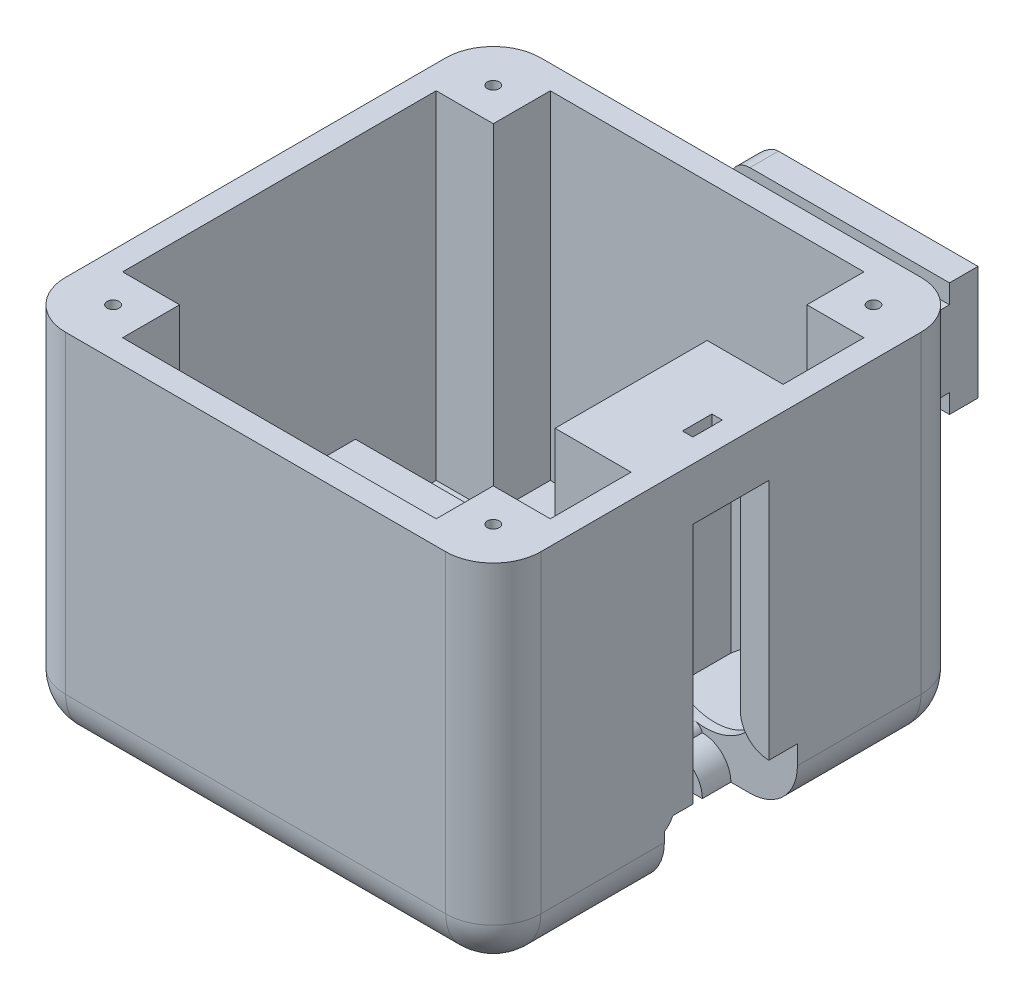
SolidWorks part; units mm, degrees
ref_plane "Front Plane" through (0, 0, 0) normal (0, 0, 1) x (1, 0, 0)
ref_plane "Top Plane" through (0, 0, 0) normal (0, 1, 0) x (1, 0, 0)
ref_plane "Right Plane" through (0, 0, 0) normal (1, 0, 0) x (0, 0, -1)
sketch "Sketch1" plane through (0, 0, 0) normal (0, 1, 0) x (1, 0, 0)
  line L1 (25, 25) -> (-25, 25)
  line L2 (25, 25) -> (25, -25)
  line L3 (25, -25) -> (-25, -25)
  line L4 (-25, 25) -> (-25, -25)
  line L5 (25, 25) -> (-25, -25) construction
  line L6 (25, -25) -> (-25, 25) construction
  point P0 (0, 0)
  dimension "D1" = 50
  dimension "D2" = 50
extrude "Boss-Extrude1" add sketch "Sketch1" along normal blind 38
shell "Shell1" thickness 2.5 removed face at (0, 38, 0)
sketch "Sketch2" plane through (0, 2.5, 0) normal (0, 1, 0) x (1, 0, 0)
  line L1 (9.676, 17.0496) -> (-10.324, 17.0496) construction
  line L2 (9.676, 17.0496) -> (9.676, -16.9504) construction
  line L3 (-10.3, -16.9504) -> (-10.324, -16.9504) construction
  line L4 (-10.324, 17.0496) -> (-10.324, -16.9504) construction
  line L5 (-10.3, 6.5) -> (-22.5, 6.5)
  line L6 (-22.5, 22.5) -> (-22.5, -22.5) construction
  line L7 (-22.5, 6.5) -> (-22.5, 22.5)
  line L8 (-22.5, 22.5) -> (0, 22.5)
  line L9 (22.5, 22.5) -> (-22.5, 22.5) construction
  line L11 (-10.3, 6.5) -> (-10.3, 13.5)
  line L12 (-10.3, 13.5) -> (0, 13.5)
  line L14 (22.5, 7.28) -> (22.5, 22.5)
  line L15 (10.3, 7.28) -> (22.5, 7.28)
  line L16 (10.3, 7.28) -> (10.3, 13.5)
  line L17 (10.3, 13.5) -> (0, 13.5)
  line L19 (22.5, 22.5) -> (0, 22.5)
  line L20 (10.3, -13.3556) -> (22.5, -13.3556)
  line L22 (10.0266, -9.8035) -> (10.0241, -17.0234) construction
  line L27 (-22.5, -13.6) -> (-22.5, -22.5)
  line L28 (-10.3, -13.6) -> (-22.5, -13.6)
  line L29 (-10.3, -13.6) -> (-10.3, -20.79)
  line L30 (-10.3, -20.79) -> (0.1901, -20.79)
  line L32 (-22.5, -22.5) -> (0.1901, -22.5)
  line L33 (-10.324, 17.0496) -> (-10.324, 9.8396) construction
  line L34 (10.3, -13.3556) -> (10.3, -20.79)
  line L35 (9.676, -16.9504) -> (-10.3, -16.9504) construction
  line L36 (10.3, -20.79) -> (0.1901, -20.79)
  line L38 (22.5, -22.5) -> (0.1901, -22.5)
  line L39 (22.5, -13.3556) -> (22.5, -22.5)
  line L40 (22.5, -22.5) -> (22.5, 22.5) construction
  point P0 (0, 0)
  dimension "D1" = 34
  dimension "D3" = 12.2
  dimension "D4" = 12.2
  dimension "D5" = 16
  dimension "D6" = 8.9
  dimension "D7" = 9
  dimension "D9" = 1.71
sketch "Sketch3" plane through (0, 2.5, 0) normal (0, 1, 0) x (1, 0, 0)
  line L0 (22.5, -8) -> (22.5, 8)
  line L1 (22.5, -22.5) -> (22.5, 22.5) construction
  line L2 (22.5, 8) -> (22.5, -8)
  line L3 (22.5, 8) -> (-22.5, 8)
  line L4 (22.5, -8) -> (-22.5, -8)
  line L5 (-22.5, 8) -> (-22.5, -8)
  line L6 (-22.5, 22.5) -> (-22.5, -22.5) construction
  point P4 (22.5, 0)
  point P6 (22.5, 0)
  line M6 (-22.5, 22.5) -> (-22.5, -22.5)
  line M8 (22.5, -22.5) -> (22.5, 22.5)
  dimension "D1" = 16
extrude "Boss-Extrude3" add sketch "Sketch3" along normal blind 8 contours L4 L3 M8 M6 region at (0, 2.5, 0)
sketch "Sketch4" plane through (0, 0, 0) normal (0, -1, 0) x (1, 0, 0)
  line L4 (25, -4) -> (-7.5, -4)
  line L5 (22.5, -8) -> (25, -8) construction
  line L6 (22.5, 8) -> (25, 8) construction
  line L7 (22.5, 0) -> (25, 0)
  line L8 (25, 25) -> (25, -25) construction
  line L9 (-7.5, -4) -> (-7.5, 4)
  line L10 (-7.5, 4) -> (25, 4)
  line L11 (25, 4) -> (25, -4)
  point P10 (25, 0)
  line M10 (25, -25) -> (25, 25)
  dimension "D1" = 8
  dimension "D2" = 32.5
extrude "Cut-Extrude1" cut sketch "Sketch4" against normal blind 3 contours L10 L9 L4 M10 region at (8.75, 0, 0)
ref_plane "Plane1" through (0, 3, 0) normal (0, -1, 0) x (-1, 0, 0)
sketch "Sketch7" plane through (0, 3, 0) normal (0, -1, 0) x (-1, 0, 0)
  line L5 (-25, 4) -> (-25, -4) construction
  line L6 (-25, -6) -> (-25, 6)
  line L7 (-25, -6) -> (7.5, -6)
  line L8 (-25, 6) -> (7.5, 6)
  line L9 (7.5, -6) -> (7.5, 6)
  line L10 (-25, -25) -> (-25, -4) construction
  line L11 (-25, 4) -> (-25, 25) construction
  point P4 (-25, 0)
  point P11 (-25, 0)
  dimension "D1" = 12
  dimension "D2" = 32.5
extrude "Cut-Extrude2" cut sketch "Sketch7" against normal blind 3
sketch "Sketch8" plane through (22.5, 0, 0) normal (-1, 0, 0) x (0, 0, 1)
  line L0 (-8, 10.5) -> (-8, 38)
  line L1 (22.5, 38) -> (-22.5, 38) construction
  line L2 (8, 10.5) -> (8, 38)
  line L3 (8, 38) -> (-8, 38)
  line L4 (-8, 10.5) -> (8, 10.5)
extrude "Boss-Extrude4" add sketch "Sketch8" along normal blind 8
sketch "Sketch9" plane through (25, 0, 0) normal (1, 0, 0) x (0, 0, -1)
  line L0 (-4, 0) -> (-4, 32.5)
  line L2 (4, 0) -> (4, 32.5)
  line L3 (4, 32.5) -> (-4, 32.5)
  line L4 (-4, 0) -> (4, 0)
  dimension "D1" = 32.5
extrude "Cut-Extrude3" cut sketch "Sketch9" against normal blind 3 contours L4 L2 L3 L0
ref_plane "Plane2" through (22, 0, 0) normal (1, 0, 0) x (0, 0, -1)
sketch "Sketch10" plane through (22, 0, 0) normal (1, 0, 0) x (0, 0, -1)
  line L0 (-6, 0) -> (-6, 32.5)
  line L1 (-25, 0) -> (-4, 0) construction
  line L3 (6, 3) -> (6, 0)
  line L4 (4, 0) -> (25, 0) construction
  line L5 (6, 0) -> (6, 32.5)
  line L7 (6, 32.5) -> (-6, 32.5)
  line L8 (-6, 0) -> (6, 0)
  dimension "D1" = 32.5
extrude "Cut-Extrude5" cut sketch "Sketch10" against normal blind 3 contours L0 L8 L3 L5 L7 region at (22, 16.25, 0)
ref_plane "Plane3" through (0, 0, 4) normal (0, 0, -1) x (-1, 0, 0)
sketch "Sketch13" plane through (0, 0, 4) normal (0, 0, -1) x (-1, 0, 0)
  line L0 (-25, 0) -> (-22, 0)
  line L1 (-25, 0) -> (-25, 3.0115)
  line L2 (-22, 0) -> (-22, 3.0115)
  line L3 (-25, 3.0115) -> (-22, 3.0115)
extrude "Cut-Extrude7" cut sketch "Sketch13" against normal blind 2 and the other way blind 10
ref_plane "Plane4" through (0, 0, 6) normal (0, 0, -1) x (-1, 0, 0)
fillet "Fillet1" radius 5 9 edges at (-25, 19, 25) (25, 19, 25) (25, 19, -25) (-25, 19, -25) (-25, 0, 0) (0, 0, 25) (25, 0, 15.5) (0, 0, -25) (25, 0, -15.5)
ref_plane "Plane6" through (0, 0, 1.5) normal (0, 0, -1) x (-1, 0, 0)
sketch "Sketch16" plane through (0, 0, 1.5) normal (0, 0, -1) x (-1, 0, 0)
  line L0 (-25, 9.7) -> (-25, 0) construction
  line L1 (-17.6, 9.7) -> (-15.3, 9.7) construction
  line L2 (-25, 0) -> (-15.3, 0) construction
  line L3 (-15.3, 9.7) -> (-15.3, 7.4) construction
  line L5 (-15.3, 7.4) -> (-15.3, 0) construction
  line L6 (-25, 9.7) -> (-17.6, 9.7) construction
  circle A0 centre (-15.3, 9.7) radius 2.3
  dimension "D3" = 4.6
  dimension "D1" = 9.7
  dimension "D2" = 9.7
extrude "Cut-Extrude8" cut sketch "Sketch16" along normal through all
sketch "Sketch17" plane through (0, 0, -25) normal (0, 0, -1) x (-1, 0, 0)
  line L0 (-20, 36) -> (3, 36)
  line L1 (-20, 38) -> (-20, 5) construction
  line L2 (3, 36) -> (3, 24)
  line L3 (3, 24) -> (-20, 24)
  line L4 (-20, 24) -> (-20, 36)
  line L5 (-20, 38) -> (20, 38) construction
  dimension "D1" = 12
  dimension "D2" = 23
  dimension "D3" = 2
extrude "Boss-Extrude5" add sketch "Sketch17" along normal blind 6
sketch "Sketch18" plane through (-3, 0, 0) normal (-1, 0, 0) x (0, 0, 1)
  line L0 (-31, 30) -> (-25, 30) construction
  line L1 (-31, 24) -> (-31, 36) construction
  line L2 (-25, 24) -> (-25, 36) construction
  line L3 (-28, 24) -> (-25, 24)
  line L4 (-28, 24) -> (-28, 26)
  line L5 (-25, 24) -> (-25, 26)
  line L6 (-28, 26) -> (-25, 26)
  line L7 (-31, 24) -> (-25, 24) construction
  line L8 (-25, 36) -> (-25, 34)
  line L9 (-28, 34) -> (-25, 34)
  line L10 (-28, 36) -> (-28, 34)
  line L11 (-28, 36) -> (-25, 36)
  dimension "D1" = 4
extrude "Cut-Extrude9" cut sketch "Sketch18" against normal through all
ref_plane "Plane5" through (0, 0, -25) normal (0, 0, -1) x (-1, 0, 0)
sketch "Sketch20" plane through (0, 0, 4) normal (0, 0, -1) x (-1, 0, 0)
  line L0 (-22, 6) -> (-22, 32.5) construction
  line L2 (-22, 10) -> (-22, 7)
  line L7 (-22, 6) -> (-25, 6) construction
  line L8 (-24, 6) -> (-22, 6)
  line L9 (-22, 6) -> (-22, 7)
  line L10 (-24, 6) -> (-25, 6)
  line L11 (-25, 6) -> (-25, 7)
  line L12 (-25, 6) -> (-25, 32.5) construction
  arc A0 (-25, 7) -> (-22, 10) centre (-25, 10) ccw
  dimension "D1" = 1
  dimension "D2" = 3
extrude "Cut-Extrude12" cut sketch "Sketch20" against normal blind 2
sketch "Sketch21" plane through (0, 0, 4) normal (0, 0, -1) x (-1, 0, 0)
  line L4 (-19, 3) -> (-19, 0)
  line L5 (-19, 0) -> (-18, 0)
  line L6 (7.5, 0) -> (-19, 0) construction
  line L7 (-19, 3) -> (-15, 3)
  line L8 (7.5, 3) -> (-19, 3) construction
  arc A3 (-18, 0) -> (-15, 3) centre (-15, 0) cw
  dimension "D1" = 4
  dimension "D2" = 1
extrude "Cut-Extrude13" cut sketch "Sketch21" against normal blind 2
sketch "Sketch22" plane through (0, 0, 4) normal (0, 0, -1) x (-1, 0, 0)
  line L1 (-15.3, 9.7) -> (-11.4116, 5)
  line L2 (-19, 6) -> (7.5, 6) construction
  line L3 (-15.3, 9.7) -> (-20, 13.5884)
  line L4 (-19, 6) -> (-19, 32.5) construction
  arc A0 (-20, 13.5884) -> (-11.4116, 5) centre (-15.3, 9.7) ccw
  arc A1 (-11.4116, 5) -> (-20, 13.5884) centre (-15.3, 9.7) ccw construction
  dimension "D1" = 12.2
  dimension "D2" = 1
  dimension "D3" = 1
extrude "Cut-Extrude14" cut sketch "Sketch22" along normal blind 16
sketch "Sketch19" plane through (0, 0, -25) normal (0, 0, -1) x (-1, 0, 0)
  line L5 (-29.317, 23.717) -> (-2.5763, -3.0237) construction
  line L6 (-8.1251, 16.8749) -> (-36.496, -11.496) construction
  line L18 (-13.3319, 10.8903) -> (-12.8016, 11.4206)
  line L19 (-12.8016, 11.4206) -> (-13.5794, 12.1984)
  line L20 (-13.5794, 12.1984) -> (-14.1097, 11.6681)
  line L21 (-17.7984, 7.9794) -> (-17.2681, 8.5097)
  line L22 (-17.0206, 7.2016) -> (-17.7984, 7.9794)
  line L23 (-16.4903, 7.7319) -> (-17.0206, 7.2016)
  arc A4 (-13.3319, 10.8903) -> (-14.1097, 11.6681) centre (-15.3, 9.7) ccw
  arc A5 (-16.4903, 7.7319) -> (-17.2681, 8.5097) centre (-15.3, 9.7) cw
  circle A6 centre (-15.3, 9.7) radius 2.3
  circle A7 centre (-15.3, 9.7) radius 2.3 construction
  point P6 (-13.0668, 11.1554)
  dimension "D1" = 4.6
  dimension "D3" = 0.75
  dimension "D2" = 1.1
extrude "Cut-Extrude10" cut sketch "Sketch19" against normal blind 19.5 contours A6 L21 L22 L23 | A6 L18 L19 L20 region at (13.4401, 11.5599, -25) region at (17.1599, 7.8401, -25)
sketch "Sketch23" plane through (0, 0, 6) normal (0, 0, -1) x (-1, 0, 0)
  line L0 (-15.3, 9.7) -> (-20.286, 10.0734)
  line L1 (-15.3, 9.7) -> (-10.4869, 11.0544)
  line L4 (-20.4743, 10.0875) -> (-20.286, 10.0734)
  circle A0 centre (-15.3, 9.7) radius 5
  dimension "D1" = 10
  dimension "D2" = 200
extrude "Cut-Extrude15" [suppressed] cut sketch "Sketch23" along normal blind 15 contours L0 A0 L1
fillet "Fillet4" radius 2 3 edges at (-3, 36, -29.5) (-3, 24, -29.5) (-3, 30, -31)
sketch "Sketch26" plane through (0, 0, 6) normal (0, 0, -1) x (-1, 0, 0)
  line L0 (-25, 6) -> (-25, 0)
  line L1 (-25, 0) -> (-19, 0)
  line L2 (-19, 0) -> (-19, 6)
  line L3 (-19, 6) -> (-25, 6)
  dimension "D1" = 6
  dimension "D2" = 6
extrude "Cut-Extrude18" cut sketch "Sketch26" against normal blind 1 and the other way blind 13
fillet "Fillet7" [suppressed] radius 2
sketch "Sketch29" plane through (0, 0, 6) normal (0, 0, -1) x (-1, 0, 0)
  line L0 (-16.4873, 10.6823) -> (-15.3138, 9.6473)
  line L1 (-15.3138, 9.6473) -> (-14.2826, 8.4703)
  line L2 (-12.2389, 6) -> (-15.3, 9.7) construction
  line L3 (-15.3, 9.7) -> (-19, 12.7611) construction
  arc A0 (-16.4873, 10.6823) -> (-14.2826, 8.4703) centre (-15.3138, 9.6473) cw
extrude "Boss-Extrude6" add sketch "Sketch29" along normal blind 4.5
sketch "Sketch30" plane through (-7.5, 0, 0) normal (1, 0, 0) x (0, 0, -1)
  line L0 (-4, 3) -> (4, 3) construction
  line L2 (-2.17, 3.9) -> (2.17, 3.9)
  line L3 (-2.17, 3.9) -> (-2.17, 2.1)
  line L4 (-2.17, 2.1) -> (2.17, 2.1)
  line L5 (2.17, 3.9) -> (2.17, 2.1)
  line L6 (-2.17, 3.9) -> (2.17, 2.1) construction
  line L7 (-2.17, 2.1) -> (2.17, 3.9) construction
  point P4 (0, 3)
  point P5 (0, 3)
  dimension "D1" = 4.34
  dimension "D2" = 1.8
extrude "Cut-Extrude19" cut sketch "Sketch30" against normal blind 4.4 contours L3 L2 L5 L4
sketch "Sketch31" plane through (0, 32.5, 0) normal (0, -1, 0) x (1, 0, 0)
  line L0 (22, 4) -> (22, -4) construction
  line L2 (21.1, 2.17) -> (22.9, 2.17)
  line L3 (21.1, 2.17) -> (21.1, -2.17)
  line L4 (21.1, -2.17) -> (22.9, -2.17)
  line L5 (22.9, 2.17) -> (22.9, -2.17)
  line L6 (21.1, 2.17) -> (22.9, -2.17) construction
  line L7 (21.1, -2.17) -> (22.9, 2.17) construction
  point P4 (22, 0)
  point P5 (22, 0)
  dimension "D1" = 4.34
  dimension "D2" = 1.8
extrude "Cut-Extrude20" cut sketch "Sketch31" against normal blind 4.4
sketch "Sketch32" plane through (0, 36.9, 0) normal (0, -1, 0) x (1, 0, 0)
  line L0 (22, -2.17) -> (22, 2.17) construction
  line L1 (21.1, -2.17) -> (22.9, -2.17) construction
  line L2 (22.9, 2.17) -> (21.1, 2.17) construction
  line L4 (21.45, 1.55) -> (22.55, 1.55)
  line L5 (21.45, 1.55) -> (21.45, -1.55)
  line L6 (21.45, -1.55) -> (22.55, -1.55)
  line L7 (22.55, 1.55) -> (22.55, -1.55)
  line L8 (21.45, 1.55) -> (22.55, -1.55) construction
  line L9 (21.45, -1.55) -> (22.55, 1.55) construction
  point P6 (22, 0)
  point P7 (22, 0)
  dimension "D1" = 3.1
  dimension "D2" = 1.1
extrude "Cut-Extrude21" cut sketch "Sketch32" against normal through all
sketch "Sketch33" plane through (-11.9, 0, 0) normal (1, 0, 0) x (0, 0, -1)
  line L0 (-2.17, 3) -> (2.17, 3) construction
  line L1 (-2.17, 3.9) -> (-2.17, 2.1) construction
  line L2 (2.17, 3.9) -> (2.17, 2.1) construction
  line L4 (1.55, 3.55) -> (-1.55, 3.55)
  line L5 (1.55, 3.55) -> (1.55, 2.45)
  line L6 (1.55, 2.45) -> (-1.55, 2.45)
  line L7 (-1.55, 3.55) -> (-1.55, 2.45)
  line L8 (1.55, 3.55) -> (-1.55, 2.45) construction
  line L9 (1.55, 2.45) -> (-1.55, 3.55) construction
  point P6 (0, 3)
  point P7 (0, 3)
  dimension "D1" = 3.1
  dimension "D2" = 1.1
extrude "Cut-Extrude22" cut sketch "Sketch33" against normal blind 3.55
sketch "Sketch34" plane through (0, 10.5, 0) normal (0, 1, 0) x (1, 0, 0)
  line L0 (-22.5, 0) -> (-13.4, 0)
  line L3 (-13.95, 1.55) -> (-12.85, 1.55)
  line L4 (-13.95, 1.55) -> (-13.95, -1.55)
  line L5 (-13.95, -1.55) -> (-12.85, -1.55)
  line L6 (-12.85, 1.55) -> (-12.85, -1.55)
  line L7 (-13.95, 1.55) -> (-12.85, -1.55) construction
  line L8 (-13.95, -1.55) -> (-12.85, 1.55) construction
  dimension "D1" = 9.1
  dimension "D2" = 3.1
  dimension "D3" = 1.1
  dimension "D4" = 8
extrude "Cut-Extrude23" cut sketch "Sketch34" against normal blind 7.3 contours L6 L3 L4 L5 region at (-13.4, 10.5, -1.5171)
sketch "Sketch44" plane through (0, 0, 4) normal (0, 0, -1) x (-1, 0, 0)
  line L0 (-19, 12.7611) -> (-19, 6)
  line L1 (-19, 6) -> (-12.2389, 6)
  line L4 (-19, 12.7611) -> (-16.4873, 10.6823)
  line L5 (-16.4873, 10.6823) -> (-15.3138, 9.6473)
  line L6 (-15.3138, 9.6473) -> (-14.2826, 8.4703)
  line L7 (-14.2826, 8.4703) -> (-12.2389, 6)
extrude "Cut-Extrude26" cut sketch "Sketch44" against normal blind 2
sketch "Sketch45" plane through (0, 0, 1.5) normal (0, 0, -1) x (-1, 0, 0)
  line L0 (-17.4095, 7.5905) -> (-13.1905, 11.8095) construction
  line L1 (-17.0206, 7.2016) -> (-17.7984, 7.9794) construction
  line L2 (-12.8016, 11.4206) -> (-13.5794, 12.1984) construction
  line L3 (-16.9263, 11.3263) -> (-13.6737, 8.0737) construction
  circle A0 centre (-15.3, 9.7) radius 3.575
  arc A4 (-14.1097, 11.6681) -> (-17.2681, 8.5097) centre (-15.3, 9.7) ccw construction
  arc A5 (-16.4903, 7.7319) -> (-13.3319, 10.8903) centre (-15.3, 9.7) ccw construction
  point P21 (-15.3, 9.7)
  dimension "D1" = 7.15
extrude "Cut-Extrude27" cut sketch "Sketch45" along normal blind 20
fillet "Fillet8" radius 2 2 edges at (19, 3, 6) (22, 6, 6)
ref_plane "Plane7" through (0, 0, -6) normal (0, 0, 1) x (1, 0, 0)
sketch "Sketch46" plane through (0, 0, -6) normal (0, 0, 1) x (1, 0, 0)
  line L0 (20.1497, 6) -> (22, 6)
  line L1 (20.1497, 6) -> (20.1497, 10)
  line L2 (22, 6) -> (22, 10)
  line L3 (20.1497, 10) -> (22, 10)
  line L4 (19, 3) -> (19, 4.8503)
  line L5 (19, 3) -> (15, 3)
  line L6 (19, 4.8503) -> (15, 4.8503)
  line L7 (15, 3) -> (15, 4.8503)
  dimension "D1" = 4
  dimension "D2" = 4
extrude "Cut-Extrude28" cut sketch "Sketch46" against normal blind 1
sketch "Sketch43" plane through (0, 0, -4) normal (0, 0, 1) x (1, 0, 0)
  line L0 (19, 0) -> (18, 0)
  line L1 (19, 0) -> (-7.5, 0) construction
  line L2 (19, 0) -> (19, 3)
  line L3 (19, 3) -> (15, 3)
  line L4 (19, 3) -> (-7.5, 3) construction
  arc A1 (18, 0) -> (15, 3) centre (15, 0) ccw
  dimension "D1" = 1
  dimension "D2" = 4
extrude "Cut-Extrude25" cut sketch "Sketch43" against normal blind 3
sketch "Sketch42" plane through (0, 0, -4) normal (0, 0, 1) x (1, 0, 0)
  line L0 (22, 6) -> (25, 6)
  line L1 (25, 6) -> (25, 7)
  line L2 (25, 6) -> (25, 32.5) construction
  line L3 (22, 6) -> (22, 10)
  line L4 (22, 6) -> (22, 32.5) construction
  arc A1 (25, 7) -> (22, 10) centre (25, 10) cw
  dimension "D1" = 4
  dimension "D2" = 1
extrude "Cut-Extrude24" cut sketch "Sketch42" against normal blind 3
fillet "Fillet9" radius 1 2 edges at (21.3926, 10, -6.5) (15, 3.6074, -6.5)
fillet "Fillet10" radius 1 2 edges at (11.8157, 10.5, -3.25) (14.5, 13.1843, -3.25)
ref_plane "Plane8" through (0, 2.5, 0) normal (0, 1, 0) x (1, 0, 0)
sketch "Sketch47" plane through (0, 2.5, 0) normal (0, 1, 0) x (1, 0, 0)
  line L0 (22.5, 22.5) -> (16.5, 22.5)
  line L1 (-22.5, 22.5) -> (-16.5, 22.5)
  line L2 (-22.5, 22.5) -> (-22.5, 16.5)
  line L3 (-22.5, 16.5) -> (-16.5, 16.5)
  line L4 (-16.5, 22.5) -> (-16.5, 16.5)
  line L5 (22.5, 22.5) -> (22.5, 16.5)
  line L6 (22.5, 16.5) -> (16.5, 16.5)
  line L7 (16.5, 22.5) -> (16.5, 16.5)
  line L8 (22.5, -22.5) -> (22.5, -16.5)
  line L9 (22.5, -22.5) -> (16.5, -22.5)
  line L10 (16.5, -22.5) -> (16.5, -16.5)
  line L11 (22.5, -16.5) -> (16.5, -16.5)
  line L12 (-22.5, -22.5) -> (-16.5, -22.5)
  line L13 (-22.5, -22.5) -> (-22.5, -16.5)
  line L14 (-22.5, -16.5) -> (-16.5, -16.5)
  line L15 (-16.5, -22.5) -> (-16.5, -16.5)
  point P20 (0, 0)
  dimension "D1" = 6
  dimension "D2" = 6
  dimension "D3" = 4
extrude "Boss-Extrude7" add sketch "Sketch47" along normal up to surface (35.5 mm away) up to face at (22, 38, 0)
hole_wizard "M1.6 Tapped Hole1" positions "Sketch50" profile "Sketch52" tap size "M1.6" standard "ISO"
sketch "Sketch50" plane through (0, 38, 0) normal (0, 1, 0) x (1, 0, 0)
  line L0 (-25, 20) -> (-25, -20) construction
  line L1 (-20, -25) -> (20, -25) construction
  point P0 (-20, -20)
  point P16 (-20, 20)
  point P17 (20, 20)
  point P18 (20, -20)
  dimension "D1" = 5
  dimension "D2" = 5
  dimension "D3" = 4
sketch "Sketch52" plane through (-20, 38, 20) normal (1, 0, 0) x (0, 0, 1)
  line L0 (0, 0) -> (0, 5.3755)
  line L1 (0, 5.3755) -> (0.625, 5)
  line L2 (0.625, 5) -> (0.625, 0)
  line L5 (0.625, 0) -> (0, 0)
  line L10 (0, 5.3755) -> (-0.625, 5) construction
  line L11 (0, -6.35) -> (0, 107.95) construction
  dimension "Tap Drill Dia." = 1.25
  dimension "Tap Drill Depth" = 5
  dimension "Drill Angle" = 118
cosmetic thread "Hole Thread1" parameters "D1"=3.2, "D2"=1.6
cosmetic thread "Hole Thread2" parameters "D1"=3.2, "D2"=1.6
cosmetic thread "Hole Thread3" parameters "D1"=3.2, "D2"=1.6
cosmetic thread "Hole Thread4" parameters "D1"=3.2, "D2"=1.6
